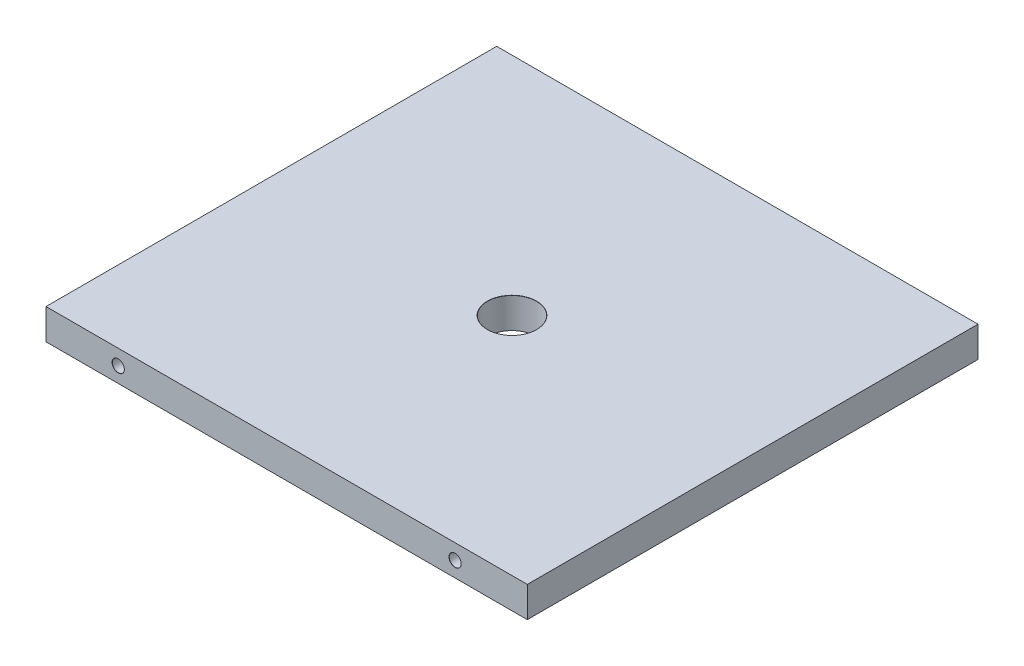
SolidWorks part; units mm, degrees
material "6061 Alloy"
ref_plane "Front Plane" through (0, 0, 0) normal (0, 0, 1) x (1, 0, 0)
ref_plane "Top Plane" through (0, 0, 0) normal (0, 1, 0) x (1, 0, 0)
ref_plane "Right Plane" through (0, 0, 0) normal (1, 0, 0) x (0, 0, -1)
sketch "Sketch1" plane through (0, 0, 0) normal (0, 1, 0) x (1, 0, 0)
  line L1 (-50, -46.825) -> (50, -46.825)
  line L2 (-50, -46.825) -> (-50, 46.825)
  line L3 (-50, 46.825) -> (50, 46.825)
  line L4 (50, -46.825) -> (50, 46.825)
  line L5 (-50, -46.825) -> (50, 46.825) construction
  line L6 (-50, 46.825) -> (50, -46.825) construction
  point P0 (0, 0)
extrude "Boss-Extrude1" add sketch "Sketch1" along normal blind 6.35
sketch "Sketch2" plane through (0, 0, 46.825) normal (0, 0, 1) x (1, 0, 0)
  line L0 (-50, 3.175) -> (-35, 3.175)
  line L1 (-50, 6.35) -> (-50, 0) construction
  line L2 (50, 3.175) -> (35, 3.175)
  line L3 (50, 6.35) -> (50, 0) construction
hole_wizard "Tap Drill for M3x0.5 Tap1" positions "Sketch3" profile "Sketch4" hole size "M3x0.5" standard "ANSI Metric"
sketch "Sketch3" plane through (0, 0, 46.825) normal (0, 0, 1) x (1, 0, 0)
  point P0 (-35, 3.175)
  point P3 (35, 3.175)
sketch "Sketch4" plane through (-35, 3.175, 46.825) normal (1, 0, 0) x (0, -1, 0)
  line L0 (0, 0) -> (0, 10)
  line L1 (0, 10) -> (1.25, 9.2489)
  line L2 (1.25, 9.2489) -> (1.25, 0.025)
  line L3 (1.25, 0.025) -> (1.275, 0)
  line L5 (1.275, 0) -> (0, 0)
  line L6 (-1.25, 0.025) -> (-1.275, 0) construction
  line L10 (0, 10) -> (-1.25, 9.2489) construction
  line L11 (0, -6.35) -> (0, 107.95) construction
  dimension "Hole Dia." = 2.5
  dimension "Hole Depth" = 10
  dimension "Near C'Sink Dia." = 2.55
  dimension "Near C'Sink Angle" = 90
  dimension "Drill Angle" = 118
sketch "Sketch5" plane through (0, 0, -46.825) normal (0, 0, -1) x (-1, 0, 0)
  line L0 (-50, 3.175) -> (-35, 3.175)
  line L1 (50, 3.175) -> (35, 3.175)
hole_wizard "Tap Drill for M3x0.5 Tap2" positions "Sketch6" profile "Sketch7" hole size "M3x0.5" standard "ANSI Metric"
sketch "Sketch6" plane through (0, 0, -46.825) normal (0, 0, -1) x (-1, 0, 0)
  point P0 (-35, 3.175)
  point P3 (35, 3.175)
sketch "Sketch7" plane through (35, 3.175, -46.825) normal (1, 0, 0) x (0, 1, 0)
  line L0 (0, 0) -> (0, 10)
  line L1 (0, 10) -> (1.25, 9.2489)
  line L2 (1.25, 9.2489) -> (1.25, 0.025)
  line L3 (1.25, 0.025) -> (1.275, 0)
  line L5 (1.275, 0) -> (0, 0)
  line L6 (-1.25, 0.025) -> (-1.275, 0) construction
  line L10 (0, 10) -> (-1.25, 9.2489) construction
  line L11 (0, -6.35) -> (0, 107.95) construction
  dimension "Hole Dia." = 2.5
  dimension "Hole Depth" = 10
  dimension "Near C'Sink Dia." = 2.55
  dimension "Near C'Sink Angle" = 90
  dimension "Drill Angle" = 118
hole_wizard "Tap Drill for M12x1.75 Tap1" positions "Sketch9" profile "Sketch10" hole size "M12x1.75" standard "ANSI Metric" end condition through all
sketch "Sketch9" plane through (0, 6.35, 0) normal (0, 1, 0) x (1, 0, 0)
  point P0 (0, 0)
sketch "Sketch10" plane through (0, 6.35, 0) normal (1, 0, 0) x (0, 0, 1)
  line L0 (0, 0) -> (0, 6.35)
  line L1 (0, 6.35) -> (5.1, 6.35)
  line L2 (5.1, 6.35) -> (5.1, 0.025)
  line L3 (5.1, 0.025) -> (5.125, 0)
  line L5 (5.125, 0) -> (0, 0)
  line L6 (-5.1, 0.025) -> (-5.125, 0) construction
  line L11 (0, -6.35) -> (0, 107.95) construction
  dimension "Thru Hole Dia." = 10.2
  dimension "Thru Hole Depth" = 6.35
  dimension "Near C'Sink Dia." = 10.25
  dimension "Near C'Sink Angle" = 90
